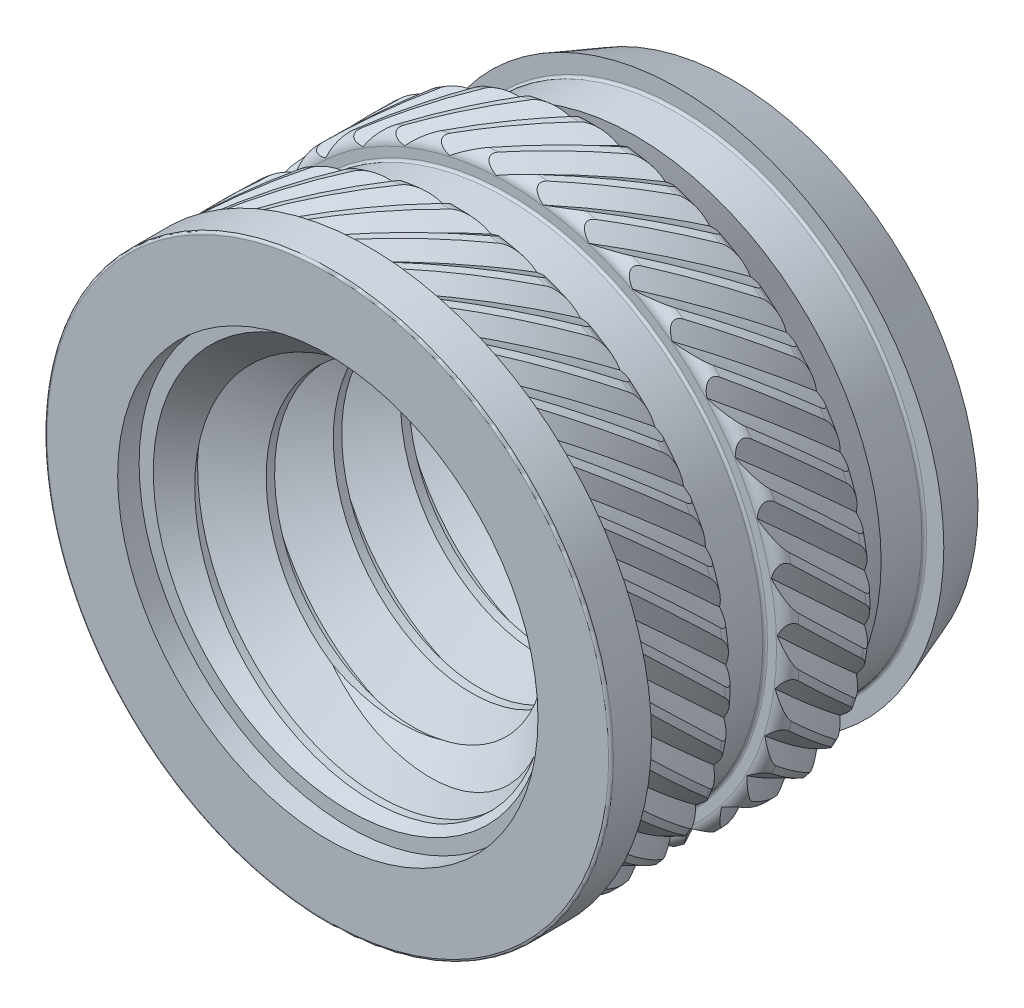
SolidWorks part; units mm, degrees
ref_plane "Front Plane" through (0, 0, 0) normal (0, 0, 1) x (1, 0, 0)
ref_plane "Top Plane" through (0, 0, 0) normal (0, 1, 0) x (1, 0, 0)
ref_plane "Right Plane" through (0, 0, 0) normal (1, 0, 0) x (0, 0, -1)
sketch "Sketch1" plane through (0, 0, 0) normal (1, 0, 0) x (0, 0, -1)
  line L0 (-4.2545, 0) -> (4.2545, 0) construction
  line L1 (-4.2545, 3.9688) -> (-4.2545, 5.9563)
  line L2 (-4.2545, 5.9563) -> (-3.4036, 5.9563)
  line L3 (-3.4036, 5.9563) -> (-3.4036, 5.8967)
  line L4 (-3.4036, 5.8967) -> (-1.5538, 5.8967)
  line L5 (-1.5538, 5.8967) -> (-1.5538, 5.4148)
  line L6 (-1.5538, 5.4148) -> (-0.473, 5.4148)
  line L7 (-0.473, 5.4148) -> (-0.473, 5.8967)
  line L11 (3.1241, 5.1639) -> (2.2165, 5.1639)
  line L14 (3.1241, 5.1639) -> (3.1241, 5.5753)
  line L15 (3.1241, 5.5753) -> (4.2545, 5.1639)
  line L16 (4.2545, 5.1639) -> (4.2545, 3.9688)
  line L17 (-4.2545, 5.5753) -> (4.2545, 5.5753) construction
  line L18 (4.2545, 0) -> (4.2545, 5.5753) construction
  line L19 (-4.2545, 0) -> (-4.2545, 5.9563) construction
  line L20 (-0.473, 5.8967) -> (1.3767, 5.8967)
  line L21 (-4.2545, 3.9688) -> (4.2545, 3.9688)
  line L22 (-4.2545, -5.5753) -> (4.2545, -5.5753) construction
  line L23 (-5.5774, 4.1215) -> (-4.8719, 2.8994) construction
  line L24 (1.3767, 5.8967) -> (1.3767, 5.6745)
  line L25 (-4.8719, 2.8994) -> (-4.1663, 4.1215) construction
  line L26 (-4.1663, 4.1215) -> (-5.5774, 4.1215) construction
  line L27 (-5.4892, 3.9688) -> (-4.2545, 3.9688) construction
  line L28 (-4.8719, 4.1215) -> (-4.8719, 3.9688) construction
  line L29 (-4.8719, 3.9688) -> (-4.8719, 3.0522) construction
  line L30 (-4.8719, 3.0522) -> (-4.8719, 2.8994) construction
  line L31 (-4.9601, 3.0522) -> (-4.7837, 3.0522)
  line L32 (-5.5333, 4.0451) -> (-4.2104, 4.0451)
  line L33 (-4.7837, 3.0522) -> (-4.2104, 4.0451)
  line L34 (-4.9601, 3.0522) -> (-5.5333, 4.0451)
  line L35 (-4.2545, 5.4737) -> (4.2545, 5.4737) construction
  line L36 (-4.2545, -5.4737) -> (4.2545, -5.4737) construction
  line L37 (1.3767, 5.6745) -> (2.2165, 5.1639)
  point P27 (-0.473, 5.6558)
  point P36 (-4.8719, 4.0451)
  dimension "Installed Length" = 8.509
  dimension "Dia A" = 11.9126
  dimension "Dia B" = 11.1506
  dimension "Thread Size" = 7.9375
  dimension "D6" = 20
  dimension "D8" = 1.8498
  dimension "Thread Pitch" = 1.4111
  dimension "D2" = 0.1764
  dimension "For Maximum Hole Diameter" = 10.9474
  dimension "D3" = 10.3277
  dimension "D1" = 0.8509
  dimension "D7" = 0.9076
  dimension "D9" = 11.7935
  dimension "Knurling Length" = 4.7803
  dimension "D4" = 10.8296
  dimension "D5" = 0.2222
ref_plane "Plane1" through (0, 0, 3.4036) normal (0, 0, 1) x (1, 0, 0)
sketch "Sketch2" plane through (0, 0, 0) normal (0, 0, 1) x (1, 0, 0)
  line L0 (0, 0) -> (0, 5.8967) construction
  line L1 (-0.4113, 5.8824) -> (0, 5.6745)
  line L2 (0.4113, 5.8824) -> (0, 5.6745)
  line L3 (-0.4113, 5.8824) -> (0, 0) construction
  line L4 (0.4113, 5.8824) -> (0, 0) construction
  line L5 (0, 0) -> (-0.7697, 5.8463) construction
  line L6 (0, 0) -> (0.7697, 5.8463) construction
  line L7 (0, 0) -> (4.1696, 4.1696) construction
  line L8 (0, 0) -> (0, -4.1215) construction
  line L9 (0, 0) -> (2.0608, -3.5693) construction
  circle A0 centre (0, 0) radius 5.6745 construction
  circle A1 centre (0, 0) radius 5.8967 construction
  arc A2 (-0.4113, 5.8824) -> (0.4113, 5.8824) centre (0, 0) cw
  circle A3 centre (0, 0) radius 4.1215
  dimension "Knurl Angle" = 8
  dimension "Pattern Angle" = 15
  dimension "Helix Angle" = 45
  dimension "D1" = 30
sketch "Sketch3" plane through (0, 0, 0) normal (1, 0, 0) x (0, 0, -1)
  line L0 (-4.2545, 3.9688) -> (-4.2545, 5.9563) construction
  line L1 (-4.2545, 5.9563) -> (-3.4036, 5.9563) construction
  line L2 (-3.4036, 5.9563) -> (-3.4036, 5.8967) construction
  line L3 (-3.4036, 5.8967) -> (-1.5538, 5.8967) construction
  line L4 (-1.5538, 5.8967) -> (-1.5538, 5.4148) construction
  line L5 (-1.5538, 5.4148) -> (-0.473, 5.4148) construction
  line L6 (-0.473, 5.4148) -> (-0.473, 5.8967) construction
  line L7 (1.3767, 5.8967) -> (1.3767, 5.6745) construction
  line L9 (3.1241, 5.1639) -> (2.2165, 5.1639) construction
  line L10 (1.3767, 5.6745) -> (2.2165, 5.1639) construction
  line L11 (1.3767, 5.8967) -> (1.3767, 5.6745) construction
  line L12 (1.3767, 5.6745) -> (2.2165, 5.1639)
  line L13 (3.1241, 5.1639) -> (3.1241, 5.5753) construction
  line L14 (3.1241, 5.5753) -> (4.2545, 5.1639) construction
  line L15 (4.2545, 5.1639) -> (4.2545, 3.9688) construction
  line L16 (-4.2545, 3.9688) -> (4.2545, 3.9688) construction
  line L17 (-4.2545, 4.4196) -> (-4.2545, 5.9055)
  line L18 (-4.2037, 5.9563) -> (-3.4036, 5.9563)
  line L19 (-3.4036, 5.9563) -> (-3.4036, 5.8967)
  line L20 (-3.4036, 5.8967) -> (-1.7948, 5.8967)
  line L21 (-1.5538, 5.6558) -> (-1.5538, 5.4656)
  line L22 (-1.503, 5.4148) -> (-0.5238, 5.4148)
  line L23 (-0.473, 5.4656) -> (-0.473, 5.6558)
  line L26 (3.0733, 5.1639) -> (2.2165, 5.1639)
  line L30 (3.1241, 5.2147) -> (3.1241, 5.5753)
  line L31 (3.1241, 5.5753) -> (4.2545, 5.1639)
  line L32 (4.2545, 5.1639) -> (4.2545, 3.9688)
  line L33 (-3.8037, 3.9688) -> (4.2545, 3.9688)
  line L34 (-0.473, 5.8967) -> (1.3767, 5.8967) construction
  line L35 (-0.2321, 5.8967) -> (1.3767, 5.8967) construction
  line L37 (-4.2545, 4.4196) -> (-3.8037, 4.4196)
  line L38 (-3.8037, 4.4196) -> (-3.8037, 3.9688)
  line L39 (-1.7948, 5.8967) -> (-1.7948, 5.4148) construction
  line L40 (-0.2321, 5.8967) -> (1.1545, 5.8967)
  arc A0 (-0.5238, 5.4148) -> (-0.473, 5.4656) centre (-0.5238, 5.4656) ccw
  arc A1 (-1.5538, 5.4656) -> (-1.503, 5.4148) centre (-1.503, 5.4656) ccw
  arc A2 (3.0733, 5.1639) -> (3.1241, 5.2147) centre (3.0733, 5.2147) ccw
  arc A3 (-0.473, 5.6558) -> (-0.2321, 5.8967) centre (-0.2321, 5.6558) cw
  arc A4 (-1.5538, 5.6558) -> (-1.7948, 5.8967) centre (-1.7948, 5.6558) ccw
  arc A5 (1.3767, 5.6745) -> (1.1545, 5.8967) centre (1.1545, 5.6745) ccw
  arc A6 (-4.2545, 5.9055) -> (-4.2037, 5.9563) centre (-4.2037, 5.9055) cw
  point P14 (-3.8037, 5.9563)
  dimension "D1" = 0.0508
  dimension "D2" = 0.0508
revolve "Revolve1" add sketch "Sketch3" angle 360 about L0
sketch "Sketch4" plane through (0, 0, 3.4036) normal (0, 0, 1) x (1, 0, 0)
  circle A2 centre (0, 0) radius 5.8967 construction
  circle A3 centre (0, 0) radius 5.8967
sketch "Sketch5" plane through (0, 0, 4.2545) normal (0, 0, 1) x (1, 0, 0)
  circle A0 centre (0, 0) radius 3.9688
curve "Helix/Spiral1" pitch 1.4111 height 9.5758 radius 3.9688 centre (0, 0, 4.2545) axis (0, 0, -1) start towards (0, 1, 0)
sketch "Sketch6" plane through (0, 0, 0) normal (1, 0, 0) x (0, 0, -1)
  line L0 (-4.9601, 3.0522) -> (-4.7837, 3.0522) construction
  line L1 (-4.9601, 3.0522) -> (-5.5333, 4.0451) construction
  line L2 (-5.5333, 4.0451) -> (-4.2104, 4.0451) construction
  line L3 (-4.7837, 3.0522) -> (-4.2104, 4.0451) construction
  line L4 (-4.9601, 3.0522) -> (-4.7837, 3.0522)
  line L5 (-4.9601, 3.0522) -> (-5.5333, 4.0451)
  line L6 (-5.5333, 4.0451) -> (-4.2104, 4.0451)
  line L7 (-4.7837, 3.0522) -> (-4.2104, 4.0451)
sweep "Sweep1" add profiles "Sketch6" path "Helix/Spiral1"
sketch "Sketch7" plane through (0, 0, 3.8037) normal (0, 0, 1) x (1, 0, 0)
  circle A0 centre (0, 0) radius 4.1215
extrude "Cut-Extrude1" cut sketch "Sketch7" against normal through all draft 45 and the other way through all
extrude "Cut-Extrude2" cut sketch "Sketch7<2>" against normal through all and the other way through all draft 45 from surface starting at face at (-0.9783, 1.2092, -4.2545)
sketch "Sketch7<2>" plane through (0, 0, 3.8037) normal (0, 0, 1) x (1, 0, 0) same geometry as "Sketch7"
curve "Helix/Spiral2" pitch 38.2427 height 5.2584 radius 5.8967 centre (0, 0, 3.4036) axis (0, 0, -1) start towards (0, 1, 0)
sketch "Sketch8" plane through (0, 0, 3.4036) normal (0, 0, 1) x (1, 0, 0)
  line L0 (-0.4113, 5.8824) -> (0, 5.6745) construction
  line L1 (0.4113, 5.8824) -> (0, 5.6745) construction
  line L2 (-0.4113, 5.8824) -> (0, 5.6745)
  line L3 (0.4113, 5.8824) -> (0, 5.6745)
  arc A0 (0.4113, 5.8824) -> (-0.4113, 5.8824) centre (0, 0) ccw construction
  arc A1 (0.4113, 5.8824) -> (-0.4113, 5.8824) centre (0, 0) ccw
sweep "Cut-Sweep1" cut profiles "Sketch8" path "Helix/Spiral2" align with end faces yes
pattern_circular "CirPattern1" count 36 over 360 about axis through (0, 0, 4.2545) along (0, 0, -1) of "Cut-Sweep1"
equation "\"D8@Sketch1\"=\"Installed Length@Sketch1\" / 4.6"
equation "\"D4@Helix/Spiral2\" = \"Knurling Length@Sketch1\" *  ( 360 / \"Helix Angle@Sketch2\" ) "
equation "\"D3@Helix/Spiral2\" = \"Knurling Length@Sketch1\" * 1.1"
equation "\"D1@CirPattern1\" =  ( \"D3@CirPattern1\" / \"Pattern Angle@Sketch2\" )  * 1.5"
equation "\"D2@Sketch1\" = \"Thread Pitch@Sketch1\" / 8"
equation "\"D4@Helix/Spiral1\" = \"Thread Pitch@Sketch1\""
equation "\"D3@Sketch1\"=\"For Maximum Hole Diameter@Sketch1\" / 1.06"
equation "\"D1@Sketch1\"=\"Installed Length@Sketch1\" * 0.1"
equation "\"D9@Sketch1\"=\"Dia A@Sketch1\"*.99"
equation "\"D4@Sketch1\"=\"Dia A@Sketch1\" / 1.1"
equation "\"Knurling Length@Sketch1\"=\"Installed Length@Sketch1\" / 1.78"
equation "\"D5@Sketch1\"=\"Dia A@Sketch1\" / 53.6"
equation "\"D7@Sketch1\"=\"Installed Length@Sketch1\" / 9.375"
